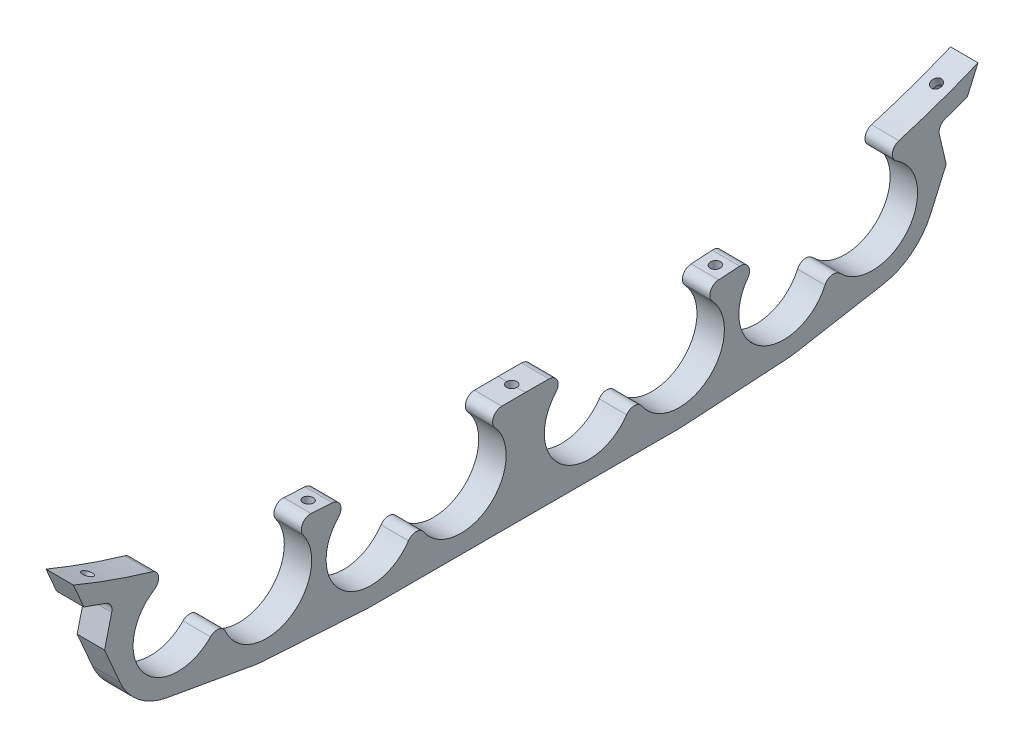
SolidWorks part; units mm, degrees
ref_plane "Front Plane" through (0, 0, 0) normal (0, 0, 1) x (1, 0, 0)
ref_plane "Top Plane" through (0, 0, 0) normal (0, 1, 0) x (1, 0, 0)
ref_plane "Right Plane" through (0, 0, 0) normal (1, 0, 0) x (0, 0, -1)
sketch "Sketch2" plane through (-4.794, 0.0207, 0) normal (-1, 0.0043, 0) x (0, 0, 1)
  line L0 (-142.0698, -17.5074) -> (-136.66, -29.9195)
  line L1 (4.0971, -50.804) -> (4.0971, -13.0673)
  line L2 (4.0971, -50.804) -> (-18.1271, -50.804)
  line L3 (-18.1271, -50.804) -> (-49.3945, -50.804)
  line L4 (-50.7864, -50.7628) -> (-87.0657, -48.5384)
  line L5 (-89.5591, -48.2419) -> (-120.3461, -42.7819)
  line L6 (4.0971, -13.0673) -> (-4.0985, -13.1033)
  line L7 (-153.0003, 7.5715) -> (-149.3123, -0.8902)
  line L8 (-141.6647, -3.6061) -> (-149.3123, -0.8902)
  line L9 (-62.968, -12.7431) -> (-70.3297, -12.2834)
  line L10 (-139.6392, -7.336) -> (-142.0698, -17.5074)
  circle A8 centre (-116.5073, -21.136) radius 15.6337 construction
  arc A9 (-124.805, -7.886) -> (-105.2301, -31.9636) centre (-116.5073, -21.136) ccw
  circle A10 centre (-85.7203, -26.5959) radius 15.6337 construction
  arc A11 (-100.0331, -32.8853) -> (-73.1278, -17.3309) centre (-85.7203, -26.5959) ccw
  circle A12 centre (-18.1737, -28.7541) radius 15.6337 construction
  circle A13 centre (-49.441, -28.8203) radius 15.6337 construction
  arc A14 (-31.1499, -37.4736) -> (-6.4742, -18.3843) centre (-18.1737, -28.7541) ccw
  arc A15 (-60.8136, -18.0929) -> (-36.428, -37.4848) centre (-49.441, -28.8203) ccw
  arc A16 (-124.805, -7.886) -> (-125.5926, -2.1497) centre (-126.4902, -5.1952) ccw
  arc A17 (-100.0331, -32.8853) -> (-105.2301, -31.9636) centre (-102.9399, -34.1626) ccw
  arc A18 (-70.3297, -12.2834) -> (-73.1278, -17.3309) centre (-70.5704, -15.4493) ccw
  arc A19 (-60.8136, -18.0929) -> (-62.968, -12.7431) centre (-63.1233, -15.9143) ccw
  arc A20 (-4.0985, -13.1033) -> (-6.4742, -18.3843) centre (-4.0982, -16.2783) ccw
  arc A21 (-31.1499, -37.4736) -> (-36.428, -37.4848) centre (-33.7852, -39.2445) ccw
  arc A26 (-50.7864, -50.7628) -> (-49.3945, -50.804) centre (-49.441, -28.8203) ccw
  arc A28 (-139.6392, -7.336) -> (-141.6647, -3.6061) centre (-142.7272, -6.5981) ccw
  arc A29 (-89.5591, -48.2419) -> (-87.0657, -48.5384) centre (-85.7203, -26.5959) ccw
  arc A31 (-136.66, -29.9195) -> (-120.3461, -42.7819) centre (-116.5073, -21.136) ccw
  spline S1 degree 3 poles (-153.0003, 7.5715) (-148.5957, 5.7339) (-140.9421, 2.779) (-133.1614, 0.1795) (-128.4533, -1.2936) (-127.0249, -1.7275) (-125.5926, -2.1497) knots 0.038381 0.038381 0.038381 0.038381 0.125 0.1875 0.1875 0.2146 0.2146 0.2146 0.2146
  dimension "D3" = 6.35
  dimension "D4" = 6.35
  dimension "D5" = 6.35
  dimension "D6" = 6.35
  dimension "D7" = 6.35
  dimension "D8" = 6.35
  dimension "D9" = 6.35
extrude "Boss-Extrude15" add sketch "Sketch2" along normal blind 4.7625 and the other way blind 4.7625
sketch "Sketch3" plane through (-0.2071, -47.8771, -17.0029) normal (-0.0041, -0.9423, -0.3347) x (1, -0.0038, -0.0014)
  line L4 (0.16, -132.2895) -> (-9.365, -132.3033)
  line L5 (-9.365, -132.3033) -> (-9.3533, -140.4188)
  line L6 (-9.3533, -140.4188) -> (0.1717, -140.405)
  line L7 (0.1717, -140.405) -> (0.16, -132.2895)
  line L8 (0.16, -132.2895) -> (-9.365, -132.3033)
  line L9 (-9.365, -132.3033) -> (-9.3533, -140.4188)
  line L10 (-9.3533, -140.4188) -> (0.1717, -140.405)
  line L11 (0.1717, -140.405) -> (0.16, -132.2895)
  circle A0 centre (-4.5908, -136.3473) radius 3.048
  dimension "D1" = 0
extrude "Cut-Extrude1" cut sketch "Sketch3" against normal blind 3.556 contours A0 region at (-4.7978, -2.2298, -145.482)
sketch "Sketch4" plane through (-0.1926, -44.5262, -15.8128) normal (-0.0041, -0.9423, -0.3347) x (-1, 0.0038, 0.0014)
  circle A0 centre (4.5908, 136.3473) radius 1.778
extrude "Cut-Extrude2" cut sketch "Sketch4" against normal blind 3.556
sketch "Sketch5" plane through (-0.2322, -53.6744, -3.291) normal (-0.0043, -0.9981, -0.0612) x (1, -0.0043, -0.0003)
  line L4 (-0.0189, -47.5846) -> (-9.5439, -47.5871)
  line L5 (-9.5439, -47.5871) -> (-9.5343, -83.9345)
  line L6 (-9.5343, -83.9345) -> (-0.0093, -83.932)
  line L7 (-0.0093, -83.932) -> (-0.0189, -47.5846)
  line L8 (-0.0189, -47.5846) -> (-9.5439, -47.5871)
  line L9 (-9.5439, -47.5871) -> (-9.5343, -83.9345)
  line L10 (-9.5343, -83.9345) -> (-0.0093, -83.932)
  line L11 (-0.0093, -83.932) -> (-0.0189, -47.5846)
  circle A0 centre (-4.7814, -65.7583) radius 3.048
  dimension "D1" = 0
extrude "Cut-Extrude3" cut sketch "Sketch5" against normal blind 3.556 contours A0 region at (-5.0136, -49.6295, -68.9248)
sketch "Sketch6" plane through (-0.2168, -50.1251, -3.0733) normal (-0.0043, -0.9981, -0.0612) x (-1, 0.0043, 0.0003)
  circle A0 centre (4.7814, 65.7583) radius 1.778
extrude "Cut-Extrude4" cut sketch "Sketch6" against normal through all
mirror "Mirror1" about plane through (-0.2513, -50.8033, 4.0971) normal (0, 0, 1) of "Cut-Extrude4", "Cut-Extrude3", "Cut-Extrude2", "Cut-Extrude1", "Boss-Extrude15"
sketch "Sketch7" plane through (-0.2198, -50.8035, 0) normal (-0.0043, -1, 0) x (1, -0.0043, 0)
  line L4 (-0.0315, -49.3945) -> (-0.0315, 57.5888)
  line L5 (-0.0315, 57.5888) -> (-9.5565, 57.5888)
  line L6 (-9.5565, 57.5888) -> (-9.5565, -49.3945)
  line L7 (-9.5565, -49.3945) -> (-0.0315, -49.3945)
  line L8 (-0.0315, -49.3945) -> (-0.0315, 57.5888)
  line L9 (-0.0315, 57.5888) -> (-9.5565, 57.5888)
  line L10 (-9.5565, 57.5888) -> (-9.5565, -49.3945)
  line L11 (-9.5565, -49.3945) -> (-0.0315, -49.3945)
  circle A0 centre (-4.794, 4.0971) radius 3.048
  dimension "D1" = 0
extrude "Cut-Extrude5" cut sketch "Sketch7" against normal blind 3.556 contours A0 region at (-5.0138, -50.7827, 4.0971)
sketch "Sketch8" plane through (-0.2044, -47.2475, 0) normal (-0.0043, -1, 0) x (-1, 0.0043, 0)
  circle A0 centre (4.794, -4.0971) radius 1.778
extrude "Cut-Extrude6" cut sketch "Sketch8" against normal through all
